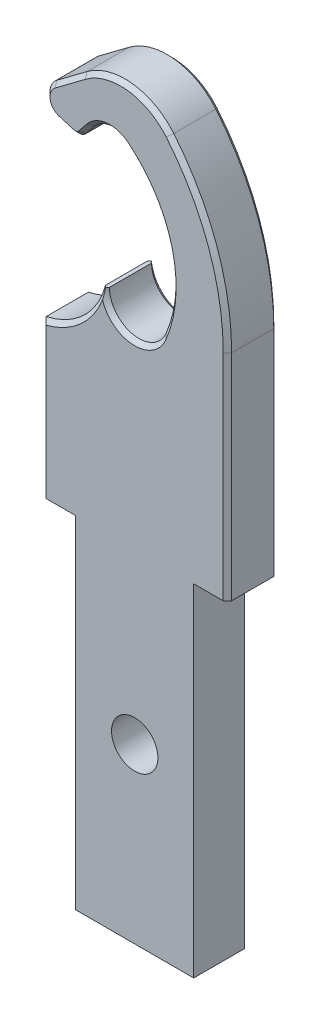
SolidWorks part; units mm, degrees
material "Q355"
ref_plane "前视基准面" through (0, 0, 0) normal (0, 0, 1) x (1, 0, 0)
ref_plane "上视基准面" through (0, 0, 0) normal (0, 1, 0) x (1, 0, 0)
ref_plane "右视基准面" through (0, 0, 0) normal (1, 0, 0) x (0, 0, -1)
sketch "草图1" plane through (0, 0, 0) normal (0, 0, 1) x (1, 0, 0)
  line L0 (140, 405) -> (180, 405)
  line L5 (0, 0) -> (140, 0)
  line L6 (0, 0) -> (0, 405)
  line L8 (140, 0) -> (140, 405)
  line L9 (180, 405) -> (180, 659.7424)
  line L10 (0, 405) -> (-40, 405)
  line L11 (-40, 405) -> (-40, 587.0673)
  line L12 (35, 654.5) -> (30.4819, 654.5)
  line L13 (-27.5, 836) -> (8.5, 863)
  line L14 (-21.3055, 800.8611) -> (-3.4028, 795.4306)
  line L15 (7.2538, 798.685) -> (17.2386, 810.9449)
  circle A0 centre (70, 205) radius 27.5
  arc A1 (35, 654.5) -> (102.2182, 640.8256) centre (70, 654.5) ccw
  arc A2 (-40, 587.0673) -> (30.4819, 654.5) centre (-59.5, 678) ccw
  arc A3 (59.5899, 815.1425) -> (17.2386, 810.9449) centre (40.5, 792) ccw
  arc A4 (-3.4028, 795.4306) -> (7.2538, 798.685) centre (-0.5, 805) ccw
  arc A5 (-27.5, 836) -> (-21.3055, 800.8611) centre (-15.5, 820) ccw
  arc A6 (111.3333, 850.7525) -> (8.5, 863) centre (53.5, 803) ccw
  arc A7 (180, 659.7424) -> (111.3333, 850.7525) centre (-120, 659.7424) ccw
  arc A8 (102.2182, 640.8256) -> (59.5899, 815.1425) centre (-35.8598, 699.4301) ccw
  dimension "D3" = 70
  dimension "D4" = 55
  dimension "D8" = 35
  dimension "D11" = 93
  dimension "D15" = 30
  dimension "D18" = 10
  dimension "D21" = 20
  dimension "D24" = 75
  dimension "D27" = 300
  dimension "D28" = 150
  dimension "D20" = 41
  dimension "D19" = 13
  dimension "D1" = 140
  dimension "D2" = 405
  dimension "D5" = 205
  dimension "D7" = 220
  dimension "D9" = 249.5
  dimension "D10" = 110
  dimension "D12" = 129.5
  dimension "D13" = 23.5
  dimension "D16" = 137.5
  dimension "D17" = 29.5
  dimension "D22" = 15
  dimension "D23" = 15
  dimension "D25" = 11
  dimension "D26" = 13
extrude "凸台-拉伸1" add sketch "草图1" along normal mid plane 60
chamfer "倒角1" distance 5 angle 45 26 edges at (4.7913, 610.8015, -30) (4.7913, 610.8015, 30) (180, 532.3712, -30) (162.3119, 761.2313, -30) (62.3698, 877.4737, -30) (-9.5, 849.5, -30) (-35.1963, 816.5278, -30) (-12.3541, 798.1459, -30) (2.4208, 795.4361, -30) (12.2462, 804.815, -30) (37.5411, 821.8537, -30) (109.8467, 735.0618, -30) (63.0228, 620.2025, -30) (180, 532.3712, 30) (162.3119, 761.2313, 30) (62.3698, 877.4737, 30) (-9.5, 849.5, 30) (-35.1963, 816.5278, 30) (-12.3541, 798.1459, 30) (2.4208, 795.4361, 30) (12.2462, 804.815, 30) (37.5411, 821.8537, 30) (109.8467, 735.0618, 30) (63.0228, 620.2025, 30) (-40, 496.0337, -30) (-40, 496.0337, 30)
